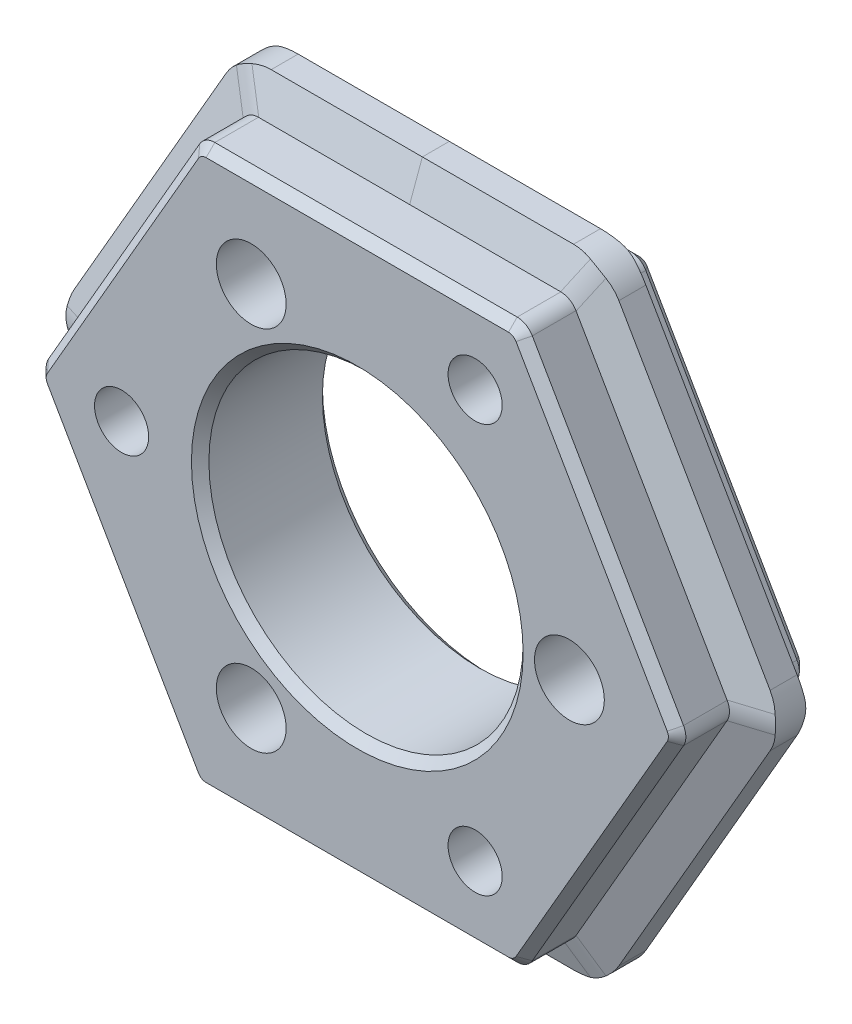
SolidWorks part; units mm, degrees
material "6061 合金"
ref_plane "前视基准面" through (0, 0, 0) normal (0, 0, 1) x (1, 0, 0)
ref_plane "上视基准面" through (0, 0, 0) normal (0, 1, 0) x (1, 0, 0)
ref_plane "右视基准面" through (0, 0, 0) normal (1, 0, 0) x (0, 0, -1)
other "Configuration Table"
sketch "草图2" plane through (0, 0, 0) normal (0, 0, 1) x (1, 0, 0)
  line L1 (9.2376, 16) -> (-9.2376, 16)
  line L2 (-9.2376, 16) -> (-18.4752, 0)
  line L3 (-18.4752, 0) -> (-9.2376, -16)
  line L4 (-9.2376, -16) -> (9.2376, -16)
  line L5 (9.2376, -16) -> (18.4752, 0)
  line L6 (18.4752, 0) -> (9.2376, 16)
  circle A0 centre (0, 0) radius 16 construction
  dimension "D1" = 32
extrude "凸台-拉伸1" add sketch "草图2" along normal mid plane 7.5
hole_wizard "M3 六角圆柱头螺钉的柱形沉头孔1" positions "草图4" profile "草图5" counterbore size "M3" standard "GB" end condition through all
sketch "草图4" plane through (0, 0, -3.75) normal (0, 0, -1) x (-1, 0, 0)
  line L0 (-18.4752, 0) -> (0, 0) construction
  line L1 (0, 0) -> (-6.75, 11.6913) construction
  circle A0 centre (0, 0) radius 13.5
  point P0 (-6.75, 11.6913)
  point P24 (13.5, 0)
  point P25 (-6.75, -11.6913)
  dimension "D1" = 27
  dimension "D2" = 60
  dimension "D3" = 3
sketch "草图5" plane through (6.75, 11.6913, -3.75) normal (1, 0, 0) x (0, 1, 0)
  line L0 (0, 0) -> (0, 7.5)
  line L1 (0, 7.5) -> (1.55, 7.5)
  line L3 (1.55, 7.5) -> (1.55, 3.1)
  line L4 (1.55, 3.1) -> (3, 3.1)
  line L5 (3, 3.1) -> (3, 0)
  line L7 (3, 0) -> (0, 0)
  line L11 (0, -6.35) -> (0, 107.95) construction
  dimension "通孔孔直径" = 3.1
  dimension "通孔孔深度" = 7.5
  dimension "柱形沉头孔直径" = 6
  dimension "柱形沉头孔深度" = 3.1
hole_wizard "Ø4.0mm 暗销孔1" positions "草图6" profile "草图7" hole size "Ø4.0" standard "GB"
sketch "草图6" plane through (0, 0, 3.75) normal (0, 0, 1) x (1, 0, 0)
  line L0 (-23.5778, 0) -> (0, 0) construction
  line L1 (0, 0) -> (-6.075, 10.5222) construction
  circle A0 centre (0, 0) radius 12.15
  point P0 (-6.075, 10.5222)
  point P19 (12.15, 0)
  point P20 (-6.075, -10.5222)
  dimension "D1" = 24.3
  dimension "D2" = 60
  dimension "D3" = 3
sketch "草图7" plane through (-6.075, 10.5222, 3.75) normal (1, 0, 0) x (0, -1, 0)
  line L0 (0, 0) -> (0, 4.2017)
  line L1 (0, 4.2017) -> (2, 3)
  line L2 (2, 3) -> (2, 0)
  line L5 (2, 0) -> (0, 0)
  line L10 (0, 4.2017) -> (-2, 3) construction
  line L11 (0, -6.35) -> (0, 107.95) construction
  dimension "孔直径" = 4
  dimension "孔深度" = 3
  dimension "导头角度" = 118
sketch "草图8" plane through (0, 0, 3.75) normal (0, 0, 1) x (1, 0, 0)
  circle A0 centre (0, 0) radius 9
  dimension "D1" = 18
extrude "切除-拉伸1" cut sketch "草图8" against normal through all
ref_plane "基准面1" through (0, 0, -0.75) normal (0, 0, -1) x (-1, 0, 0)
sketch "草图10" plane through (0, 0, -0.75) normal (0, 0, -1) x (-1, 0, 0)
  line L6 (-9.2376, 16) -> (-18.4752, 0)
  line L7 (-18.4752, 0) -> (-9.2376, -16)
  line L8 (-9.2376, -16) -> (9.2376, -16)
  line L9 (9.2376, -16) -> (18.4752, 0)
  line L10 (18.4752, 0) -> (9.2376, 16)
  line L11 (9.2376, 16) -> (-9.2376, 16)
  line L12 (-9.2376, 16) -> (-18.4752, 0)
  line L13 (-18.4752, 0) -> (-9.2376, -16)
  line L14 (-9.2376, -16) -> (9.2376, -16)
  line L15 (9.2376, -16) -> (18.4752, 0)
  line L16 (18.4752, 0) -> (9.2376, 16)
  line L17 (9.2376, 16) -> (-9.2376, 16)
  dimension "D1" = 0
sketch "草图11" plane through (0, 0, 0) normal (1, 0, 0) x (0, 0, -1)
  line L0 (0.75, 16) -> (0.75, 0) construction
  line L1 (0.75, 16) -> (0.75, -0.3955) construction
  line L2 (-0.75, 16) -> (-0.0221, 18)
  line L3 (-3.75, 16) -> (3.75, 16) construction
  line L4 (-0.0221, 18) -> (1.5221, 18)
  line L5 (1.5221, 18) -> (2.25, 16)
  line L6 (2.25, 16) -> (-0.75, 16)
  dimension "D1" = 2
  dimension "D2" = 40
  dimension "D3" = 3
sweep "扫描1" add profiles "草图11" path "草图10"
fillet "圆角1" radius 3 18 edges at (10.3923, 18, -0.75) (20.7846, 0, -0.75) (10.3923, -18, -0.75) (-10.3923, -18, -0.75) (-20.7846, 0, -0.75) (-10.3923, 18, -0.75) (-9.815, -17, -1.886) (9.815, -17, -1.886) (19.6299, 0, -1.886) (9.815, 17, -1.886) (-9.815, 17, -1.886) (-19.6299, 0, -1.886) (9.815, 17, 0.386) (-9.815, 17, 0.386) (-19.6299, 0, 0.386) (-9.815, -17, 0.386) (9.815, -17, 0.386) (19.6299, 0, 0.386)
fillet "圆角2" radius 1 12 edges at (-9.2376, -16, 2.2265) (9.2376, -16, 2.2265) (18.4752, 0, 2.2265) (9.2376, 16, 2.2265) (-9.2376, 16, 2.2265) (-18.4752, 0, 2.2265) (-18.4752, 0, -2.9765) (-9.2376, -16, -2.9765) (9.2376, -16, -2.9765) (18.4752, 0, -2.9765) (9.2376, 16, -2.9765) (-9.2376, 16, -2.9765)
chamfer "倒角1" distance 0.5 angle 45 26 edges at (9, 0, 3.75) (9, 0, -3.75) (-13.8564, 8, 3.75) (-18.3205, 0, 3.75) (-9.1603, 15.866, 3.75) (-13.8564, -8, 3.75) (0, 16, 3.75) (-9.1603, -15.866, 3.75) (9.1603, 15.866, 3.75) (0, -16, 3.75) (13.8564, 8, 3.75) (9.1603, -15.866, 3.75) (18.3205, 0, 3.75) (13.8564, -8, 3.75) (0, 16, -3.75) (-9.1603, 15.866, -3.75) (9.1603, 15.866, -3.75) (-13.8564, 8, -3.75) (13.8564, 8, -3.75) (-18.3205, 0, -3.75) (18.3205, 0, -3.75) (-13.8564, -8, -3.75) (13.8564, -8, -3.75) (-9.1603, -15.866, -3.75) (9.1603, -15.866, -3.75) (0, -16, -3.75)
